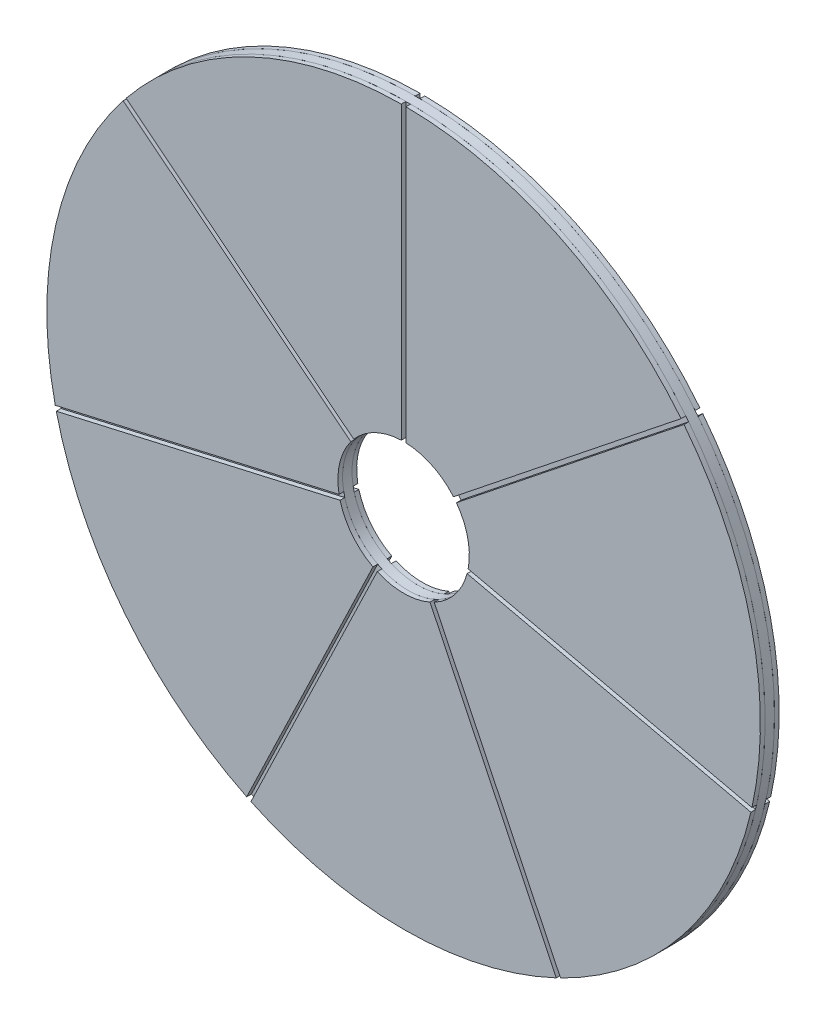
SolidWorks part; units mm, degrees
ref_plane "Front Plane" through (0, 0, 0) normal (0, 0, 1) x (1, 0, 0)
ref_plane "Top Plane" through (0, 0, 0) normal (0, 1, 0) x (1, 0, 0)
ref_plane "Right Plane" through (0, 0, 0) normal (1, 0, 0) x (0, 0, -1)
sketch "Sketch1" plane through (0, 0, 0) normal (0, 0, 1) x (1, 0, 0)
  circle A0 centre (0, 0) radius 19
  dimension "D1" = 38
extrude "Boss-Extrude1" add sketch "Sketch1" along normal blind 0.25 and the other way blind 0.25 contours A0
sketch "Sketch2" plane through (0, 0, 0.25) normal (0, 0, 1) x (1, 0, 0)
  line L0 (-0.0779, 0.0977) -> (0.0779, -0.0977)
  line L1 (-0.125, 0) -> (0.125, 0)
  line L2 (-0.125, 0) -> (-0.125, 19.4123)
  line L3 (-0.125, 19.4123) -> (0.125, 19.4123)
  line L4 (0.125, 0) -> (0.125, 19.4123)
  line L5 (-0.0779, 0.0977) -> (15.0992, 12.2011)
  line L6 (15.0992, 12.2011) -> (15.255, 12.0056)
  line L7 (0.0779, -0.0977) -> (15.255, 12.0056)
  line L8 (0.0278, 0.1219) -> (-0.0278, -0.1219)
  line L9 (0.0278, 0.1219) -> (18.9534, -4.1978)
  line L10 (18.9534, -4.1978) -> (18.8977, -4.4415)
  line L11 (-0.0278, -0.1219) -> (18.8977, -4.4415)
  line L12 (0.1126, 0.0542) -> (-0.1126, -0.0542)
  line L13 (0.1126, 0.0542) -> (8.5353, -17.4356)
  line L14 (8.5353, -17.4356) -> (8.31, -17.5441)
  line L15 (-0.1126, -0.0542) -> (8.31, -17.5441)
  line L16 (0.1126, -0.0542) -> (-0.1126, 0.0542)
  line L17 (0.1126, -0.0542) -> (-8.31, -17.5441)
  line L18 (-8.31, -17.5441) -> (-8.5353, -17.4356)
  line L19 (-0.1126, 0.0542) -> (-8.5353, -17.4356)
  line L20 (0.0278, -0.1219) -> (-0.0278, 0.1219)
  line L21 (0.0278, -0.1219) -> (-18.8977, -4.4415)
  line L22 (-18.8977, -4.4415) -> (-18.9534, -4.1978)
  line L23 (-0.0278, 0.1219) -> (-18.9534, -4.1978)
  line L24 (-0.0779, -0.0977) -> (0.0779, 0.0977)
  line L25 (-0.0779, -0.0977) -> (-15.255, 12.0056)
  line L26 (-15.255, 12.0056) -> (-15.0992, 12.2011)
  line L27 (0.0779, 0.0977) -> (-15.0992, 12.2011)
  circle A0 centre (0, 0) radius 19
  point P7 (0, 0)
  point P15 (0, 0)
  point P19 (0, 0)
  point P21 (0, 0)
  point P26 (0, 0)
  point P31 (0, 0)
  point P36 (0, 0)
  point P41 (0, 0)
  point P42 (0, 0)
  circle M1 centre (0, 0) radius 19
  dimension "D1" = 7
  dimension "D2" = 38
extrude "Boss-Extrude2" add sketch "Sketch2" along normal blind 0.25 separate body contours L4 L5 M1 | L27 L2 M1 | L23 L25 M1 | L19 L21 M1 | L15 L17 M1 | L11 L13 M1 | L7 L9 M1 region at (5.3601, 11.1303, 0.25) region at (-5.3601, 11.1303, 0.25) region at (-12.044, 2.749, 0.25) region at (12.044, 2.749, 0.25) region at (9.6585, -7.7024, 0.25) region at (0, -12.3537, 0.25) region at (-9.6585, -7.7024, 0.25)
mirror "Mirror5" about plane through (0, 0, 0) normal (0, 0, 1) of bodies 125 124 144 122 120 123 143 104 103 102 141
sketch "Sketch3" plane through (0, 0, 0) normal (0, 0, 1) x (1, 0, 0)
  circle A0 centre (0, 0) radius 3.5
  dimension "D1" = 7
extrude "Cut-Extrude2" cut sketch "Sketch3" against normal blind 8.35 and the other way blind 10 contours A0
